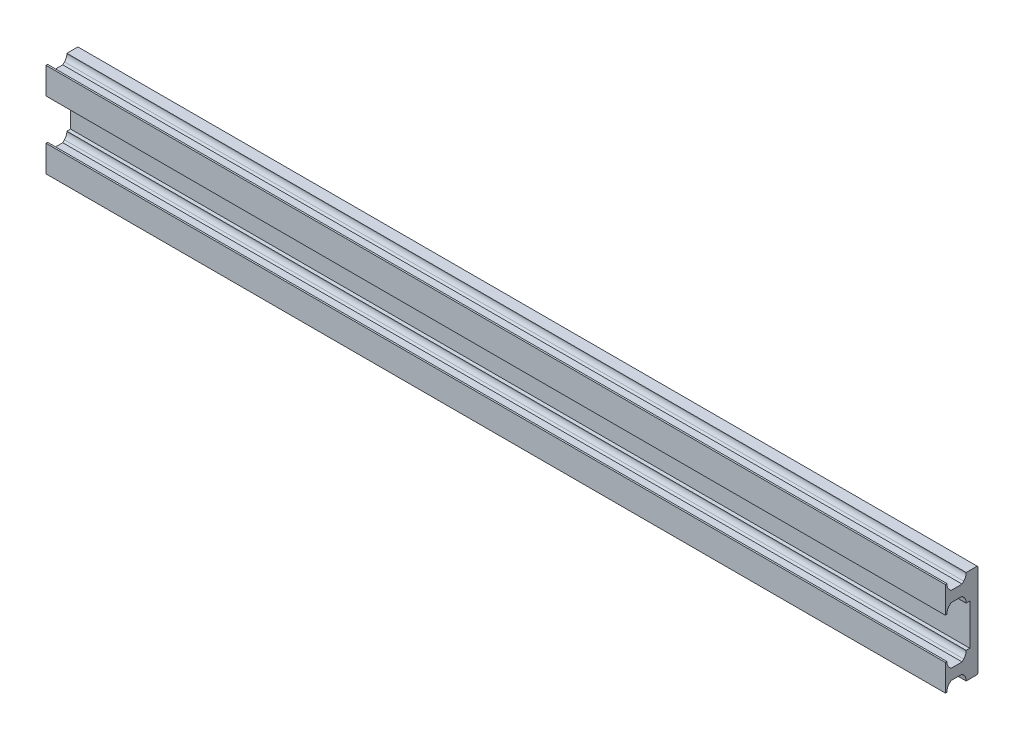
SolidWorks part; units mm, degrees
ref_plane "Front" through (0, 0, 0) normal (0, 0, 1) x (1, 0, 0)
ref_plane "Top" through (0, 0, 0) normal (0, 1, 0) x (1, 0, 0)
ref_plane "Right" through (0, 0, 0) normal (1, 0, 0) x (0, 0, -1)
sketch "Sketch1" plane through (0, 0, 0) normal (0, 0, 1) x (1, 0, 0)
  line L0 (-110, -4.5) -> (-110, 4.5) construction
  line L1 (110, 11.5) -> (-110, 11.5)
  line L2 (110, 11.5) -> (110, -11.5)
  line L3 (110, -11.5) -> (-110, -11.5)
  line L4 (-110, 11.5) -> (-110, -11.5)
  line L5 (110, 11.5) -> (-110, -11.5) construction
  line L6 (110, -11.5) -> (-110, 11.5) construction
  line L8 (110, 4.5) -> (-110, 4.5) construction
  point P0 (0, 0)
  dimension "D1" = 7
extrude "Boss-Extrude1" add sketch "Sketch1" against normal blind 2
sketch "Sketch2" plane through (0, 0, 0) normal (0, 0, 1) x (1, 0, 0)
  line L0 (-110, 11.5) -> (-110, -11.5) construction
  line L1 (110, 11.5) -> (-110, 11.5)
  line L2 (110, 11.5) -> (110, 5)
  line L3 (110, 5) -> (-110, 5)
  line L4 (-110, 11.5) -> (-110, 5)
  line L5 (110, -11.5) -> (110, 11.5) construction
  line L6 (110, -11.5) -> (-110, -11.5)
  line L7 (110, -11.5) -> (110, -5)
  line L8 (110, -5) -> (-110, -5)
  line L9 (-110, -11.5) -> (-110, -5)
  line L11 (110, 4.5) -> (-110, 4.5) construction
  dimension "D1" = 0.5
extrude "Boss-Extrude2" add sketch "Sketch2" along normal offset from surface (6 mm away) 1
ref_plane "Center of Slots" through (0, 8.25, 0) normal (0, -1, 0) x (-1, 0, 0)
sketch "Sketch5" plane through (0, 0, 0) normal (1, 0, 0) x (0, 0, -1)
  line L16 (-1.9, 6.95) -> (-4.6, 6.95)
  line L17 (-1.9, 6.95) -> (-4.6, 6.95)
  line L18 (-1.4858, 6.5358) -> (-1.9, 6.95)
  line L19 (-1.4858, 6.5358) -> (-1.9, 6.95)
  line L20 (-0.9, 4.3784) -> (-0.9, 5.1216)
  line L21 (-0.9, 4.3784) -> (-0.9, 5.1216)
  line L22 (-1.9, 2.55) -> (-1.4858, 2.9642)
  line L23 (-1.9, 2.55) -> (-1.4858, 2.9642)
  line L24 (-4.6, 2.55) -> (-1.9, 2.55)
  line L25 (-4.6, 2.55) -> (-1.9, 2.55)
  line L26 (-5.0142, 2.9642) -> (-4.6, 2.55)
  line L27 (-5.0142, 2.9642) -> (-4.6, 2.55)
  line L28 (-5.6, 5.1216) -> (-5.6, 4.3784)
  line L29 (-5.6, 5.1216) -> (-5.6, 4.3784)
  line L30 (-4.6, 6.95) -> (-5.0142, 6.5358)
  line L31 (-4.6, 6.95) -> (-5.0142, 6.5358)
  arc A12 (-0.9, 5.1216) -> (-1.4858, 6.5358) centre (-2.9, 5.1216) ccw
  arc A13 (-0.9, 5.1216) -> (-1.4858, 6.5358) centre (-2.9, 5.1216) ccw
  arc A14 (-1.4858, 2.9642) -> (-0.9, 4.3784) centre (-2.9, 4.3784) ccw
  arc A15 (-1.4858, 2.9642) -> (-0.9, 4.3784) centre (-2.9, 4.3784) ccw
  arc A16 (-5.6, 4.3784) -> (-5.0142, 2.9642) centre (-3.6, 4.3784) ccw
  arc A17 (-5.6, 4.3784) -> (-5.0142, 2.9642) centre (-3.6, 4.3784) ccw
  arc A18 (-5.0142, 6.5358) -> (-5.6, 5.1216) centre (-3.6, 5.1216) ccw
  arc A19 (-5.0142, 6.5358) -> (-5.6, 5.1216) centre (-3.6, 5.1216) ccw
  dimension "D1" = 0
extrude "Middle Slot" cut sketch "Sketch5" against normal through all both and the other way through all
mirror "Middle Slots" about plane through (0, 0, 0) normal (0, 1, 0) of "Middle Slot"
sketch "Sketch7" plane through (0, 0, 0) normal (1, 0, 0) x (0, 0, -1)
  line L8 (-1.875, 13.925) -> (-4.625, 13.925)
  line L9 (-1.4858, 13.5358) -> (-1.875, 13.925)
  line L10 (-0.9, 11.3784) -> (-0.9, 12.1216)
  line L11 (-1.9, 9.55) -> (-1.4858, 9.9642)
  line L12 (-4.6, 9.55) -> (-1.9, 9.55)
  line L13 (-5.0142, 9.9642) -> (-4.6, 9.55)
  line L14 (-5.6, 12.1216) -> (-5.6, 11.3784)
  line L15 (-4.625, 13.925) -> (-5.0142, 13.5358)
  line L16 (-1.875, 13.925) -> (-4.625, 13.925)
  line L17 (-1.4858, 13.5358) -> (-1.875, 13.925)
  line L18 (-0.9, 11.3784) -> (-0.9, 12.1216)
  line L19 (-1.9, 9.55) -> (-1.4858, 9.9642)
  line L20 (-4.6, 9.55) -> (-1.9, 9.55)
  line L21 (-5.0142, 9.9642) -> (-4.6, 9.55)
  line L22 (-5.6, 12.1216) -> (-5.6, 11.3784)
  line L23 (-4.625, 13.925) -> (-5.0142, 13.5358)
  arc A4 (-0.9, 12.1216) -> (-1.4858, 13.5358) centre (-2.9, 12.1216) ccw
  arc A5 (-1.4858, 9.9642) -> (-0.9, 11.3784) centre (-2.9, 11.3784) ccw
  arc A6 (-5.6, 11.3784) -> (-5.0142, 9.9642) centre (-3.6, 11.3784) ccw
  arc A7 (-5.0142, 13.5358) -> (-5.6, 12.1216) centre (-3.6, 12.1216) ccw
  arc A8 (-0.9, 12.1216) -> (-1.4858, 13.5358) centre (-2.9, 12.1216) ccw
  arc A9 (-1.4858, 9.9642) -> (-0.9, 11.3784) centre (-2.9, 11.3784) ccw
  arc A10 (-5.6, 11.3784) -> (-5.0142, 9.9642) centre (-3.6, 11.3784) ccw
  arc A11 (-5.0142, 13.5358) -> (-5.6, 12.1216) centre (-3.6, 12.1216) ccw
  dimension "D1" = 0
extrude "Top Slot" cut sketch "Sketch7" against normal through all both and the other way through all
mirror "Top Slots" about plane through (0, 0, 0) normal (0, 1, 0) of "Top Slot"
chamfer "Deburs" distance 0.2 angle 45 2 edges at (0, -11.5, -2) (0, 11.5, -2)
